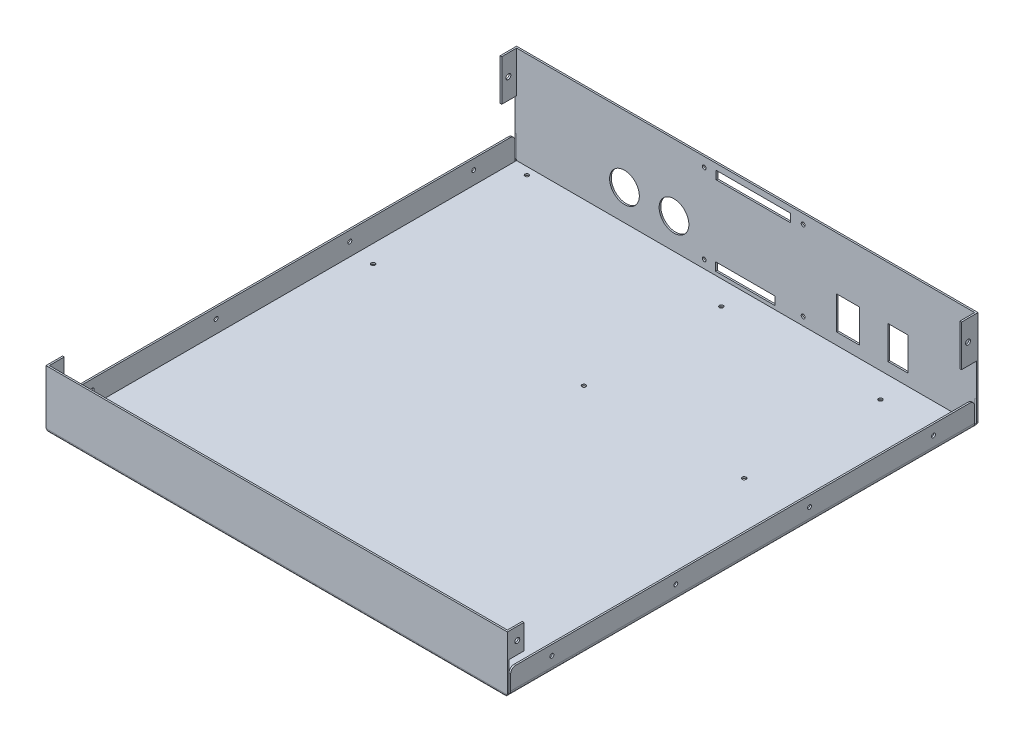
SolidWorks part; units mm, degrees
material "AISI 1015 Steel, Cold Drawn (SS)"
ref_plane "Front Plane" through (0, 0, 0) normal (0, 0, 1) x (1, 0, 0)
ref_plane "Top Plane" through (0, 0, 0) normal (0, 1, 0) x (1, 0, 0)
ref_plane "Right Plane" through (0, 0, 0) normal (1, 0, 0) x (0, 0, -1)
sketch "Sketch6" plane through (0, 0, 0) normal (0, 1, 0) x (1, 0, 0)
  line L1 (0, -162.3156) -> (279.4, -162.3156)
  line L2 (0, -162.3156) -> (0, 122.6844)
  line L3 (0, 122.6844) -> (279.4, 122.6844)
  line L4 (279.4, -162.3156) -> (279.4, 122.6844)
  dimension "D1" = 285
  dimension "D2" = 279.4
extrude "Boss-Extrude2" add sketch "Sketch6" along normal blind 60
sketch "Sketch8" plane through (0, 0, 0) normal (1, 0, 0) x (0, 0, -1)
  line L0 (-162.3156, 35) -> (-161.3156, 35)
  line L1 (-162.3156, 60) -> (-162.3156, 0) construction
  line L2 (-161.3156, 35) -> (-161.3156, 15)
  line L3 (-161.3156, 15) -> (121.6844, 15)
  line L4 (121.6844, 15) -> (121.6844, 60)
  line L5 (-162.3156, 60) -> (122.6844, 60) construction
  line L6 (121.6844, 60) -> (-162.3156, 60)
  line L7 (-162.3156, 60) -> (-162.3156, 35)
  line L8 (122.6844, 60) -> (122.6844, 0) construction
  line L9 (-162.3156, 0) -> (122.6844, 0) construction
  dimension "D1" = 1
  dimension "D2" = 1
  dimension "D3" = 15
  dimension "D4" = 35
extrude "Cut-Extrude7" cut sketch "Sketch8" against normal blind 60 and the other way through all from offset 30
shell "Shell1" thickness 1 removed face at (139.7, 15, 19.8156)
sketch "Sketch9" plane through (0, 0, -122.6844) normal (0, 0, -1) x (-1, 0, 0)
  line L0 (-279.4, 60) -> (0, 60) construction
  line L1 (-279.4, 60) -> (-279.4, 0) construction
  line L2 (-279.4, 0) -> (0, 0) construction
  line L3 (0, 60) -> (0, 0) construction
  line L4 (-279.4, 60) -> (0, 60)
  line L5 (-279.4, 60) -> (-279.4, 3)
  line L6 (-276.4, 0) -> (-3, 0)
  line L7 (0, 60) -> (0, 3)
  arc A0 (-276.4, 0) -> (-279.4, 3) centre (-276.4, 3) cw
  arc A1 (-3, 0) -> (0, 3) centre (-3, 3) ccw
  dimension "D1" = 3
extrude "Cut-Extrude8" cut sketch "Sketch9" against normal through all flip side to cut
sketch "Sketch11" plane through (279.4, 0, 0) normal (1, 0, 0) x (0, 0, -1)
  line L0 (-162.3156, 0) -> (122.6844, 0) construction
  line L1 (-161.3156, 15) -> (-157.3156, 15)
  line L2 (-161.3156, 15) -> (-161.3156, 1.9)
  line L3 (-160.4156, 1) -> (-160.3156, 1)
  line L4 (-160.3156, 12) -> (-160.3156, 1)
  line L6 (121.6836, 15.0003) -> (117.6836, 15.0003)
  line L7 (121.6836, 15.0003) -> (121.6836, 1.9)
  line L8 (120.7836, 1) -> (120.6836, 1)
  line L9 (120.6836, 12.0003) -> (120.6836, 1)
  arc A0 (120.7836, 1) -> (121.6836, 1.9) centre (120.7836, 1.9) ccw
  arc A1 (-161.3156, 1.9) -> (-160.4156, 1) centre (-160.4156, 1.9) ccw
  arc A2 (120.6836, 12.0003) -> (117.6836, 15.0003) centre (117.6836, 12.0003) ccw
  arc A3 (-160.3156, 12) -> (-157.3156, 15) centre (-157.3156, 12) cw
  dimension "D5" = 0.9
  dimension "D6" = 0.9
  dimension "D3" = 3
  dimension "D2" = 1
  dimension "D4" = 1
extrude "Cut-Extrude11" cut sketch "Sketch11" against normal through all
fillet "Fillet2" radius 2 2 edges at (139.7, 0, -122.6844) (139.7, 0, 162.3156) tangent propagation no
sketch "Sketch13" plane through (279.4, 0, 0) normal (1, 0, 0) x (0, 0, -1)
  line L0 (-157.3156, 15) -> (117.7237, 15) construction
  line L1 (-19.816, 3) -> (-19.816, 69.1905) construction
  line L2 (-160.3156, 3) -> (120.6836, 3) construction
  line L3 (-160.3156, 9) -> (141.1101, 9) construction
  line L4 (-160.3156, 3) -> (-160.3156, 12) construction
  circle A0 centre (-135.3156, 9) radius 1.5
  circle A1 centre (-60.3156, 9) radius 1.5
  circle A2 centre (20.6836, 9) radius 1.5
  circle A3 centre (95.6836, 9) radius 1.5
  dimension "D1" = 3
  dimension "D3" = 25
  dimension "D2" = 6
  dimension "D4" = 2
sketch "Sketch14" plane through (279.4, 0, 0) normal (1, 0, 0) x (0, 0, -1)
  line L0 (-162.3156, 35) -> (-162.3156, 3) construction
  line L1 (-162.3156, 35) -> (-152.3156, 35)
  line L2 (-162.3156, 35) -> (-162.3156, 20)
  line L3 (-162.3156, 20) -> (-152.3156, 20)
  line L4 (-152.3156, 35) -> (-152.3156, 20)
  line L5 (122.6844, 60) -> (112.6844, 60)
  line L6 (122.6844, 60) -> (122.6844, 35)
  line L7 (122.6844, 35) -> (112.6844, 35)
  line L8 (112.6844, 60) -> (112.6844, 35)
  line L9 (-162.3156, 35) -> (-161.3156, 35) construction
  dimension "D1" = 10
  dimension "D2" = 25
  dimension "D3" = 10
  dimension "D4" = 15
extrude "Boss-Extrude3" add sketch "Sketch14" against normal blind 1
sketch "Sketch15" plane through (0, 0, 0) normal (-1, 0, 0) x (0, 0, 1)
  line L1 (152.3156, 35) -> (162.3156, 35)
  line L2 (152.3156, 35) -> (152.3156, 20)
  line L3 (152.3156, 20) -> (162.3156, 20)
  line L4 (162.3156, 35) -> (162.3156, 20)
  line L5 (-112.6844, 60) -> (-122.6844, 60)
  line L6 (-112.6844, 60) -> (-112.6844, 35)
  line L7 (-112.6844, 35) -> (-122.6844, 35)
  line L8 (-122.6844, 60) -> (-122.6844, 35)
  dimension "D1" = 10
  dimension "D2" = 25
  dimension "D3" = 10
  dimension "D4" = 15
extrude "Boss-Extrude4" add sketch "Sketch15" against normal blind 1
sketch "Sketch16" plane through (0, 0, 0) normal (-1, 0, 0) x (0, 0, 1)
  line L0 (162.3156, 35) -> (162.3156, 3) construction
  line L1 (-122.6844, 60) -> (-122.6844, 3) construction
  circle A0 centre (156.3156, 27.5) radius 1.5
  circle A1 centre (-116.6844, 47.5) radius 1.5
  dimension "D1" = 6
  dimension "D2" = 6
extrude "Cut-Extrude14" cut sketch "Sketch16" against normal through all
sketch "Sketch36" plane through (0, 0, -122.6844) normal (0, 0, -1) x (-1, 0, 0)
  line L0 (-279.4, 60) -> (-279.4, 3) construction
  line L1 (-194.6663, 8) -> (-208.6663, 8)
  line L2 (-194.6663, 8) -> (-194.6663, 28)
  line L3 (-194.6663, 28) -> (-208.6663, 28)
  line L4 (-208.6663, 8) -> (-208.6663, 28)
  line L5 (-279.2284, 2) -> (-0.1716, 2) construction
  line L6 (-237.9, 28) -> (-225.9, 28)
  line L7 (-237.9, 28) -> (-237.9, 8)
  line L8 (-237.9, 8) -> (-225.9, 8)
  line L9 (-225.9, 28) -> (-225.9, 8)
  line L11 (-166.8765, 51.3214) -> (-121.8765, 51.3214)
  line L12 (-166.8765, 51.3214) -> (-166.8765, 56.3214)
  line L13 (-166.8765, 56.3214) -> (-121.8765, 56.3214)
  line L14 (-121.8765, 51.3214) -> (-121.8765, 56.3214)
  line L15 (-166.8765, 51.3214) -> (-121.8765, 56.3214) construction
  line L16 (-166.8765, 56.3214) -> (-121.8765, 51.3214) construction
  line L17 (-157.5724, 3.1942) -> (-121.5724, 3.1942)
  line L18 (-157.5724, 3.1942) -> (-157.5724, 8.1942)
  line L19 (-157.5724, 8.1942) -> (-121.5724, 8.1942)
  line L20 (-121.5724, 3.1942) -> (-121.5724, 8.1942)
  line L21 (-157.5724, 3.1942) -> (-121.5724, 8.1942) construction
  line L22 (-157.5724, 8.1942) -> (-121.5724, 3.1942) construction
  circle A0 centre (-96.3065, 19.6) radius 9
  circle A1 centre (-66.3065, 19.6) radius 9
  point P12 (-144.3765, 53.8214)
  point P17 (-139.5724, 5.6942)
  dimension "D13" = 18
  dimension "D14" = 18
  dimension "D1" = 14
  dimension "D2" = 20
  dimension "D3" = 12
  dimension "D4" = 20
  dimension "D5" = 6
  dimension "D6" = 6
  dimension "D7" = 17.2337
  dimension "D8" = 41.5
  dimension "D9" = 5
  dimension "D10" = 5
  dimension "D11" = 45
  dimension "D12" = 36
extrude "Cut-Extrude15" cut sketch "Sketch36" against normal blind 2
hole_wizard "3/32 (0.09375) Diameter Hole5" positions "Sketch38" profile "Sketch37" hole size "3/32" standard "ANSI Inch" end condition through all
sketch "Sketch38" plane through (279.4, 0, 0) normal (1, 0, 0) x (0, 0, -1)
  point P0 (-135.3156, 9)
  point P3 (-60.3156, 9)
  point P6 (20.6836, 9)
  point P9 (95.6836, 9)
sketch "Sketch37" plane through (279.4, 9, 135.3156) normal (0, 1, 0) x (0, 0, -1)
  line L0 (0, 0) -> (0, 279.4)
  line L1 (0, 279.4) -> (1.1906, 279.4)
  line L2 (1.1906, 279.4) -> (1.1906, 0)
  line L5 (1.1906, 0) -> (0, 0)
  line L11 (0, -6.35) -> (0, 107.95) construction
  dimension "Thru Hole Dia." = 2.3812
  dimension "Thru Hole Depth" = 279.4
hole_wizard "3/32 (0.09375) Diameter Hole8" positions "Sketch44" profile "Sketch43" hole size "3/32" standard "ANSI Inch"
sketch "Sketch44" plane through (0, 0, 0) normal (0, -1, 0) x (-1, 0, 0)
  point P0 (-11.8038, 117.1444)
  point P3 (-139.4692, 107.1444)
  point P6 (-236.5063, 106.5227)
  point P9 (-236.5063, 23.9727)
  point P12 (-139.4692, 23.9727)
  point P15 (-11.8038, 23.9727)
sketch "Sketch43" plane through (11.8038, 0, -117.1444) normal (1, 0, 0) x (0, 0, -1)
  line L0 (0, 0) -> (0, 2.7154)
  line L1 (0, 2.7154) -> (1.1906, 2)
  line L2 (1.1906, 2) -> (1.1906, 0)
  line L5 (1.1906, 0) -> (0, 0)
  line L10 (0, 2.7154) -> (-1.1906, 2) construction
  line L11 (0, -6.35) -> (0, 107.95) construction
  dimension "Hole Dia." = 2.3812
  dimension "Hole Depth" = 2
  dimension "Drill Angle" = 118
hole_wizard "3/32 (0.09375) Diameter Hole9" positions "Sketch49" profile "Sketch48" hole size "3/32" standard "ANSI Inch"
sketch "Sketch49" plane through (0, 0, -122.6844) normal (0, 0, -1) x (-1, 0, 0)
  point P0 (-174.5265, 6.0037)
  point P3 (-114.6065, 6.0037)
  point P6 (-114.6065, 54.2637)
  point P9 (-174.5265, 54.2637)
sketch "Sketch48" plane through (174.5265, 6.0037, -122.6844) normal (1, 0, 0) x (0, 1, 0)
  line L0 (0, 0) -> (0, 2.7154)
  line L1 (0, 2.7154) -> (1.1906, 2)
  line L2 (1.1906, 2) -> (1.1906, 0)
  line L5 (1.1906, 0) -> (0, 0)
  line L10 (0, 2.7154) -> (-1.1906, 2) construction
  line L11 (0, -6.35) -> (0, 107.95) construction
  dimension "Hole Dia." = 2.3812
  dimension "Hole Depth" = 2
  dimension "Drill Angle" = 118
